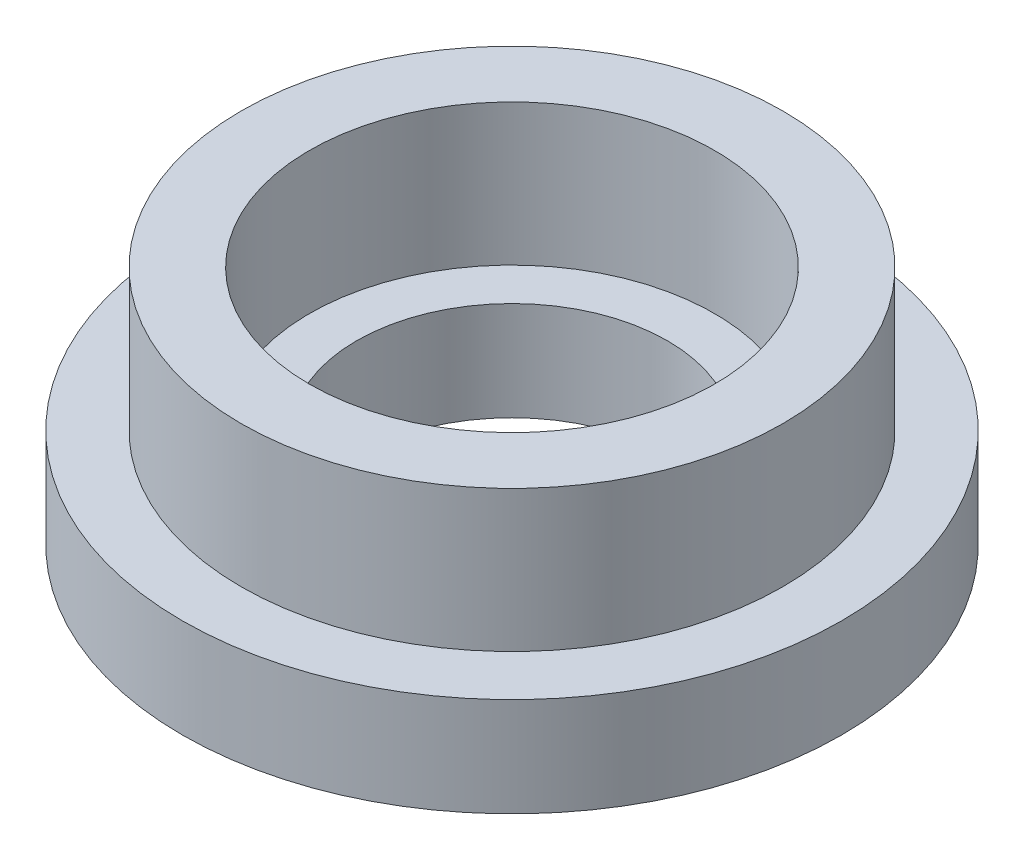
SolidWorks part; units mm, degrees
ref_plane "Front Plane" through (0, 0, 0) normal (0, 0, 1) x (1, 0, 0)
ref_plane "Top Plane" through (0, 0, 0) normal (0, 1, 0) x (1, 0, 0)
ref_plane "Right Plane" through (0, 0, 0) normal (1, 0, 0) x (0, 0, -1)
ref_axis "X-Axis" through (-88.99, 0, 0) along (1, 0, 0)
ref_axis "Y-Axis" through (0, 55, 0) along (0, -1, 0)
ref_axis "Z-Axis" through (0, 0, 55) along (0, 0, -1)
sketch "Sketch1" plane through (0, 0, 0) normal (0, 0, 1) x (1, 0, 0)
  line L1 (-5.75, 3) -> (-4.3, 3)
  line L2 (-5.75, 3) -> (-5.75, 0)
  line L4 (-4.3, 3) -> (-4.3, 0)
  line L5 (0, 55) -> (0, -55) construction
  line L6 (-7, 0) -> (-5.75, 0)
  line L7 (-7, 0) -> (-7, -2.1)
  line L8 (-7, -2.1) -> (-3.3, -2.1)
  line L11 (-4.3, 0) -> (-3.3, 0)
  line L14 (-3.3, 0) -> (-3.3, -2.1)
  line L15 (-88.99, 0) -> (88.99, 0) construction
  point P7 (-5.75, 1.5)
  dimension "D1" = 3.3
  dimension "D2" = 5.75
  dimension "D3" = 5.1
  dimension "D4" = 3
  dimension "D5" = 4.3
  dimension "D6" = 7
revolve "Revolve1" add sketch "Sketch1" angle 360 about axis through (0, 55, 0) along (0, -1, 0)
